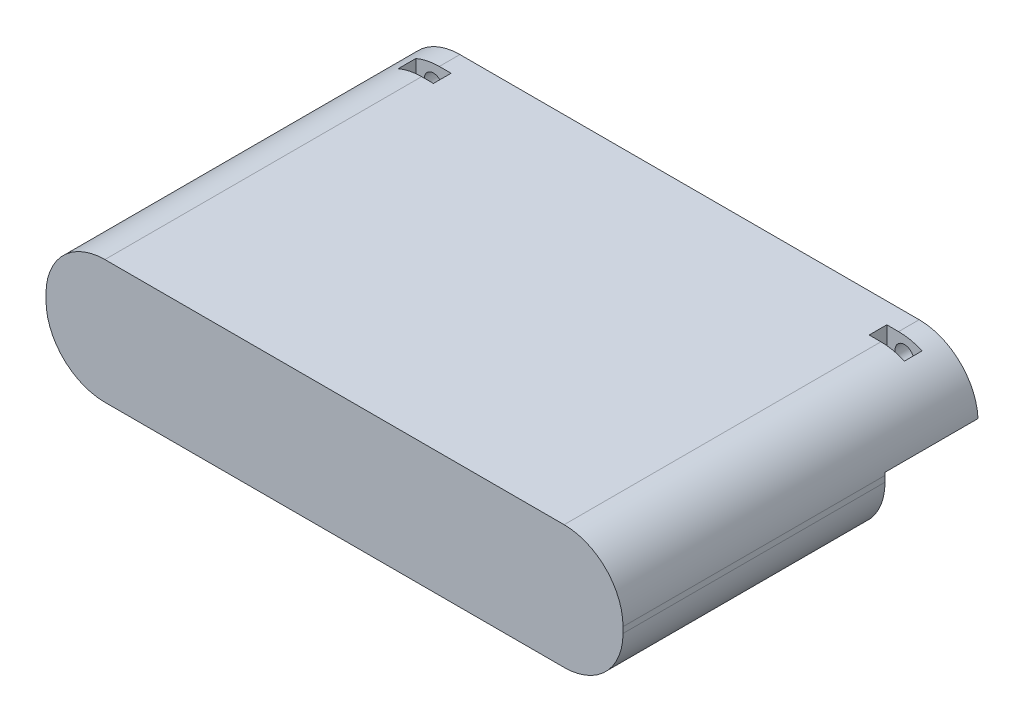
SolidWorks part; units mm, degrees
ref_plane "前视基准面" through (0, 0, 0) normal (0, 0, 1) x (1, 0, 0)
ref_plane "上视基准面" through (0, 0, 0) normal (0, 1, 0) x (1, 0, 0)
ref_plane "右视基准面" through (0, 0, 0) normal (1, 0, 0) x (0, 0, -1)
sketch "草图1" plane through (0, 0, 0) normal (0, 0, 1) x (1, 0, 0)
  line L0 (0, 10.5) -> (0, -10.5)
  line L1 (-49, 10.5) -> (49, 10.5)
  line L2 (-49, 10.5) -> (-49, -10.5)
  line L3 (-49, -10.5) -> (49, -10.5)
  line L4 (49, 10.5) -> (49, -10.5)
  line L5 (-49, 10.5) -> (49, -10.5) construction
  line L6 (-49, -10.5) -> (49, 10.5) construction
  circle A0 centre (-40, 7.5) radius 1.6
  circle A1 centre (40, 7.5) radius 1.6
  circle A2 centre (-40, -4.5) radius 4.1
  circle A3 centre (40, -4.5) radius 4.1
  circle A4 centre (40, 7.5) radius 1.6
  circle A5 centre (-40, 7.5) radius 1.6
  point P0 (0, 0)
  dimension "D3" = 9
  dimension "D4" = 3
  dimension "D5" = 9
  dimension "D1" = 98
  dimension "D2" = 21
  dimension "D6" = 12
extrude "凸台-拉伸1" add sketch "草图1" along normal blind 57.8 contours L2 L3 L0 L1 A2 A0 | A2 | A0 | L4 L1 L0 L3 A1 A3 | A3 | A1 region at (23.5258, 0.1832, 0) region at (-23.5258, 0.1832, 0) region at (-40, 7.5, 0) region at (40, 7.5, 0) region at (-40, -4.5, 0) region at (40, -4.5, 0)
sketch "草图4" plane through (0, 0, 0) normal (0, 0, -1) x (-1, 0, 0)
  line L0 (-49, -10.5) -> (-49, 0.95)
  line L1 (-49, 10.5) -> (-49, -10.5) construction
  line L2 (-49, 0.95) -> (49, 0.95)
  line L3 (49, 10.5) -> (49, -10.5) construction
  line L4 (49, 0.95) -> (49, -10.5)
  line L5 (49, -10.5) -> (-49, -10.5)
  dimension "D1" = 11.45
extrude "切除-拉伸3" cut sketch "草图4" against normal blind 15.8
sketch "草图5" plane through (0, 0, 15.8) normal (0, 0, -1) x (-1, 0, 0)
  circle A0 centre (-40, -4.5) radius 4.1
  circle A1 centre (40, -4.5) radius 4.1
extrude "切除-拉伸4" cut sketch "草图5" against normal blind 42
sketch "草图6" plane through (0, 0, 57.8) normal (0, 0, 1) x (1, 0, 0)
  line L1 (-49, 10.5) -> (49, 10.5)
  line L2 (-49, 10.5) -> (-49, -10.5)
  line L3 (-49, -10.5) -> (49, -10.5)
  line L4 (49, 10.5) -> (49, -10.5)
  line L5 (-49, 10.5) -> (49, -10.5) construction
  line L6 (-49, -10.5) -> (49, 10.5) construction
extrude "凸台-拉伸2" add sketch "草图6" along normal blind 2.5
sketch "草图7" plane through (0, 0, 0) normal (0, 0, -1) x (-1, 0, 0)
  circle A0 centre (-40, 7.5) radius 1.6
  circle A1 centre (40, 7.5) radius 1.5342
extrude "切除-拉伸5" cut sketch "草图7" against normal blind 10
sketch "草图8" plane through (0, 10.5, 0) normal (0, 1, 0) x (1, 0, 0)
  line L0 (-38.4658, 0) -> (-41.5342, 0) construction
  line L1 (-43, -3.5) -> (-37, -3.5)
  line L2 (-43, -3.5) -> (-43, -6.5)
  line L3 (-43, -6.5) -> (-37, -6.5)
  line L4 (-37, -3.5) -> (-37, -6.5)
  line L5 (-43, -3.5) -> (-37, -6.5) construction
  line L6 (-43, -6.5) -> (-37, -3.5) construction
  line L9 (43, -6.5) -> (37, -6.5)
  line L10 (43, -3.5) -> (43, -6.5)
  line L11 (43, -3.5) -> (37, -3.5)
  line L12 (37, -3.5) -> (37, -6.5)
  point P0 (-40, -5)
  dimension "D1" = 5
  dimension "D2" = 6
  dimension "D3" = 3
extrude "切除-拉伸6" cut sketch "草图8" against normal blind 7
fillet "圆角1" radius 10 1 edges at (49, 10.5, 30.15)
fillet "圆角2" radius 10 1 edges at (-49, 10.5, 30.15)
fillet "圆角3" radius 10 1 edges at (-49, -10.5, 38.05)
fillet "圆角4" radius 10 1 edges at (49, -10.5, 38.05)
